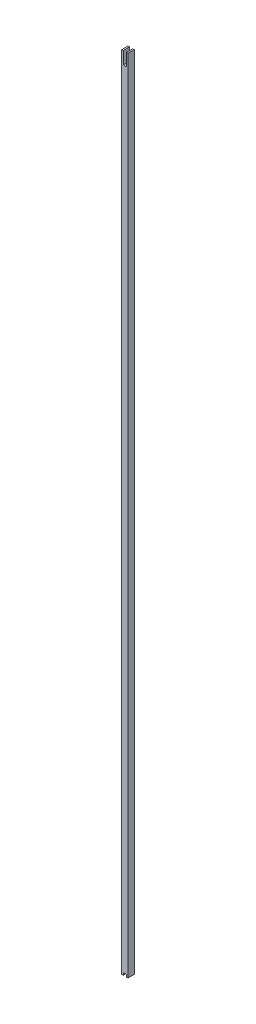
SolidWorks part; units mm, degrees
ref_plane "Front Plane" through (0, 0, 0) normal (0, 0, 1) x (1, 0, 0)
ref_plane "Top Plane" through (0, 0, 0) normal (0, 1, 0) x (1, 0, 0)
ref_plane "Right Plane" through (0, 0, 0) normal (1, 0, 0) x (0, 0, -1)
sketch "Sketch1" plane through (0, 0, 0) normal (0, 0, 1) x (1, 0, 0)
  line L0 (0, 0) -> (1.5875, 0)
  line L1 (1.5875, 0) -> (1.5875, 2.3812)
  line L2 (1.5875, 2.3812) -> (4.7625, 2.3812)
  line L3 (4.7625, 2.3812) -> (4.7625, 0)
  line L4 (4.7625, 0) -> (6.35, 0)
  line L5 (6.35, 0) -> (6.35, 812.8)
  line L6 (6.35, 812.8) -> (4.7625, 812.8)
  line L7 (4.7625, 812.8) -> (4.7625, 800.1)
  line L8 (4.7625, 800.1) -> (1.5875, 800.1)
  line L9 (1.5875, 800.1) -> (1.5875, 812.8)
  line L10 (1.5875, 812.8) -> (0, 812.8)
  line L11 (0, 812.8) -> (0, 0)
  dimension "D1" = 1.5875
  dimension "D2" = 2.3812
  dimension "D3" = 3.175
  dimension "D4" = 2.3812
  dimension "D5" = 1.5875
  dimension "D6" = 812.8
  dimension "D7" = 1.5875
  dimension "D8" = 12.7
  dimension "D9" = 3.175
  dimension "D10" = 12.7
extrude "Boss-Extrude1" add sketch "Sketch1" along normal blind 6.35
